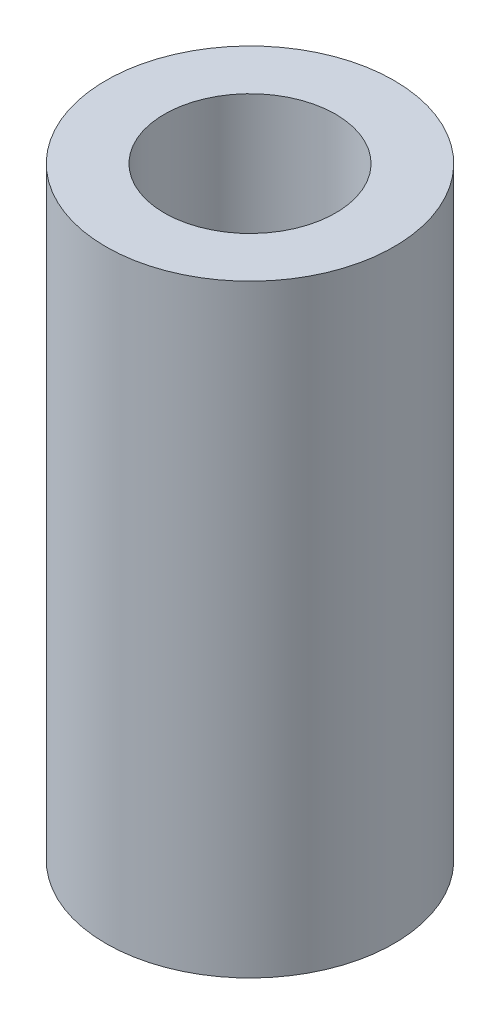
SolidWorks part; units mm, degrees
material "Rubber"
ref_plane "Front Plane" through (0, 0, 0) normal (0, 0, 1) x (1, 0, 0)
ref_plane "Top Plane" through (0, 0, 0) normal (0, 1, 0) x (1, 0, 0)
ref_plane "Right Plane" through (0, 0, 0) normal (1, 0, 0) x (0, 0, -1)
sketch "Sketch1" plane through (0, 0, 0) normal (0, 0, 1) x (1, 0, 0)
  line L0 (0, 0) -> (0, 56.388)
  dimension "D1" = 56.388
sweep "Sweep1" add path "Sketch1" circular profile diameter 26.924 parameters "D3"=26.924
sweep "Cut-Sweep1" cut path "Sketch1<3>" circular profile diameter 16.002 parameters "D3"=16.002
sketch "Sketch1<3>" plane through (0, 0, 0) normal (0, 0, 1) x (1, 0, 0) same geometry as "Sketch1"
